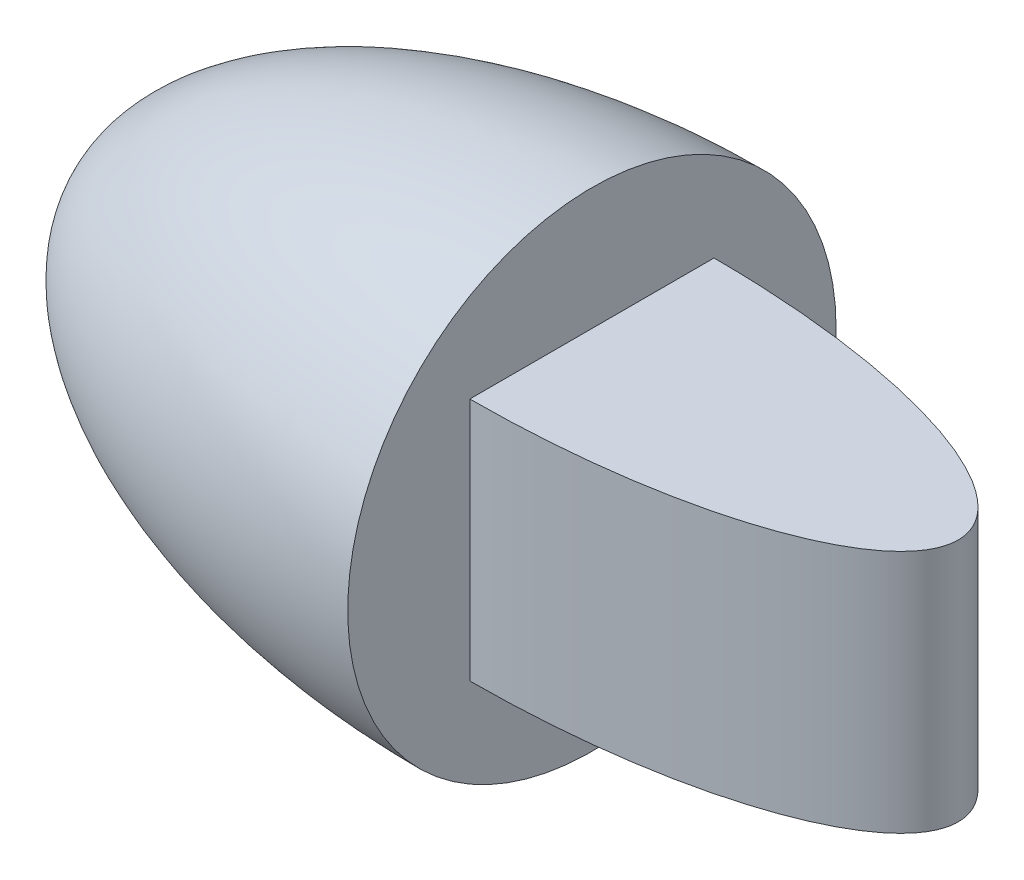
SolidWorks part; units mm, degrees
ref_plane "Alzado" through (0, 0, 0) normal (0, 0, 1) x (1, 0, 0)
ref_plane "Planta" through (0, 0, 0) normal (0, 1, 0) x (1, 0, 0)
ref_plane "Vista lateral" through (0, 0, 0) normal (1, 0, 0) x (0, 0, -1)
sketch "Sketch1" plane through (0, 0, 0) normal (0, 1, 0) x (1, 0, 0)
  line L0 (-75, 0) -> (75, 0) construction
  ellipse E0 centre (0, 0) end of major axis (75, 0) minor radius 25
  dimension "D1" = 50
  dimension "D2" = 150
extrude "Boss-Extrude1" add sketch "Sketch1" along normal blind 25 and the other way blind 25
sketch "Sketch2" plane through (0, 25, 0) normal (0, 1, 0) x (1, 0, 0)
  line L0 (0, 0) -> (75, 0) construction
  ellipse E0 centre (0, 0) end of major axis (75, 0) minor radius 25 construction
  point P9 (50, 0)
  point P10 (49.2169, 0)
  point P11 (0, 0)
  dimension "D1" = 25
ref_axis "Axis1" through (50, 25, 0) along (0, 1, 0)
sketch "Sketch3" plane through (0, 0, 0) normal (0, 1, 0) x (1, 0, 0)
  line L0 (0, 0) -> (-100, 0)
  line L1 (0, 0) -> (0, 50)
  ellipse E0 centre (0, 0) end of major axis (-100, 0) minor radius 50 (-100, 0) -> (0, 50) cw
  point P3 (-75, 0)
  point P4 (-91.4161, 0)
  point P10 (0, 42.6537)
  point P11 (0, -48.9071)
  point P12 (122.4785, 0)
  point P13 (84.007, 0)
  point P15 (0, 45.5478)
  point P16 (-75, 0)
  point P17 (-75, 0)
  point P18 (-75, 0)
  point P19 (-75, 0)
  point P20 (-75, 0)
  dimension "D1" = 100
  dimension "D2" = 50
revolve "Revolve1" add sketch "Sketch3" angle 360 about L0
